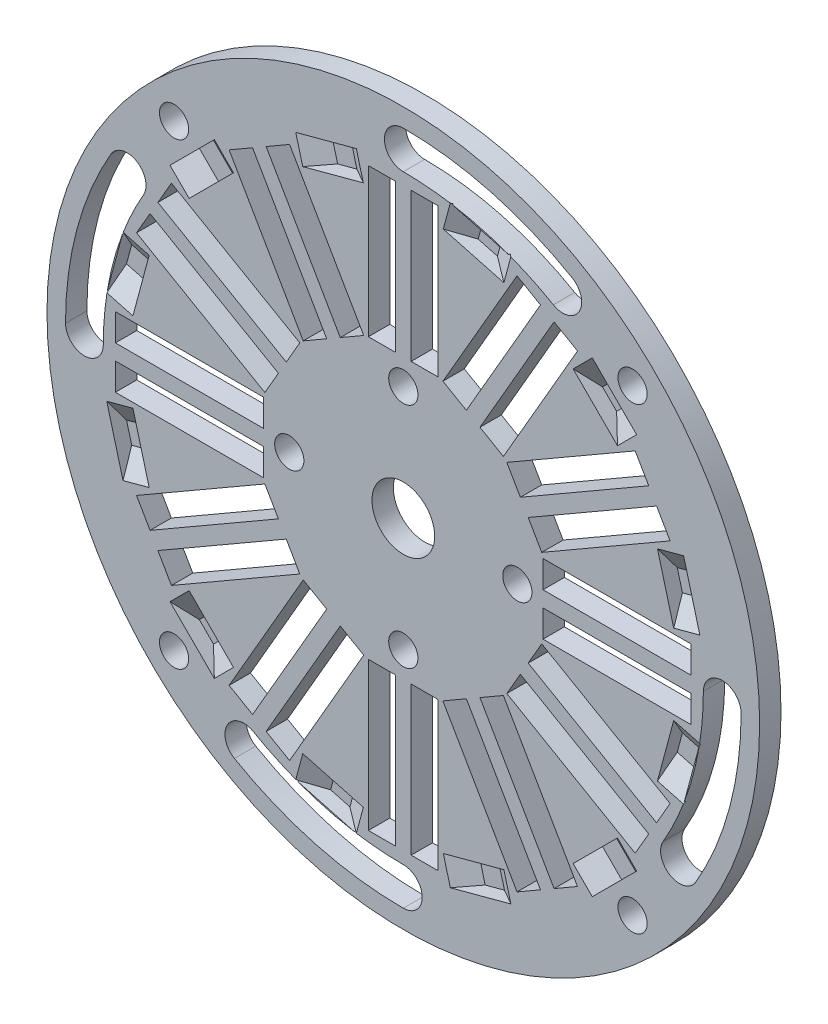
SolidWorks part; units mm, degrees
material "AISI 304"
ref_plane "Alzado" through (0, 0, 0) normal (1, 0, 0) x (0, 1, 0)
ref_plane "Planta" through (0, 0, 0) normal (0, 0, 1) x (0, 1, 0)
ref_plane "Vista lateral" through (0, 0, 0) normal (0, 1, 0) x (-1, 0, 0)
sketch "Croquis1" plane through (0, 0, 0) normal (0, 0, 1) x (0, 1, 0)
  circle A0 centre (0, 0) radius 50
  dimension "D1" = 100
extrude "Saliente-Extruir1" add sketch "Croquis1" along normal blind 3
sketch "Croquis2" plane through (0, 0, 3) normal (0, 0, 1) x (1, 0, 0)
  line L102 (15.9565, 37.4374) -> (5.5565, 19.4241)
  line L103 (-4.9, 40.4) -> (4.9, 40.4)
  line L104 (-4.9, 40.4) -> (-4.9, 19.6)
  line L105 (-4.9, 19.6) -> (4.9, 19.6)
  line L106 (4.9, 40.4) -> (4.9, 19.6)
  line L107 (-4.9, 40.4) -> (4.9, 19.6) construction
  line L108 (-4.9, 19.6) -> (4.9, 40.4) construction
  line L109 (15.9565, 37.4374) -> (24.4435, 32.5374)
  line L110 (24.4435, 32.5374) -> (14.0435, 14.5241)
  line L111 (5.5565, 19.4241) -> (14.0435, 14.5241)
  line L112 (32.5374, 24.4435) -> (14.5241, 14.0435)
  line L113 (32.5374, 24.4435) -> (37.4374, 15.9565)
  line L114 (37.4374, 15.9565) -> (19.4241, 5.5565)
  line L115 (14.5241, 14.0435) -> (19.4241, 5.5565)
  line L116 (40.4, 4.9) -> (19.6, 4.9)
  line L117 (40.4, 4.9) -> (40.4, -4.9)
  line L118 (40.4, -4.9) -> (19.6, -4.9)
  line L119 (19.6, 4.9) -> (19.6, -4.9)
  line L120 (37.4374, -15.9565) -> (19.4241, -5.5565)
  line L121 (37.4374, -15.9565) -> (32.5374, -24.4435)
  line L122 (32.5374, -24.4435) -> (14.5241, -14.0435)
  line L123 (19.4241, -5.5565) -> (14.5241, -14.0435)
  line L124 (24.4435, -32.5374) -> (14.0435, -14.5241)
  line L125 (24.4435, -32.5374) -> (15.9565, -37.4374)
  line L126 (15.9565, -37.4374) -> (5.5565, -19.4241)
  line L127 (14.0435, -14.5241) -> (5.5565, -19.4241)
  line L128 (4.9, -40.4) -> (4.9, -19.6)
  line L129 (4.9, -40.4) -> (-4.9, -40.4)
  line L130 (-4.9, -40.4) -> (-4.9, -19.6)
  line L131 (4.9, -19.6) -> (-4.9, -19.6)
  line L132 (-15.9565, -37.4374) -> (-5.5565, -19.4241)
  line L133 (-15.9565, -37.4374) -> (-24.4435, -32.5374)
  line L135 (-24.4435, -32.5374) -> (-14.0435, -14.5241)
  line L136 (-5.5565, -19.4241) -> (-14.0435, -14.5241)
  line L181 (-32.5374, -24.4435) -> (-14.5241, -14.0435)
  line L182 (-32.5374, -24.4435) -> (-37.4374, -15.9565)
  line L185 (-37.4374, -15.9565) -> (-19.4241, -5.5565)
  line L187 (-14.5241, -14.0435) -> (-19.4241, -5.5565)
  line L188 (-40.4, -4.9) -> (-19.6, -4.9)
  line L192 (-40.4, -4.9) -> (-40.4, 4.9)
  line L206 (-40.4, 4.9) -> (-19.6, 4.9)
  line L212 (-19.6, -4.9) -> (-19.6, 4.9)
  line L213 (-37.4374, 15.9565) -> (-19.4241, 5.5565)
  line L214 (-37.4374, 15.9565) -> (-32.5374, 24.4435)
  line L215 (-32.5374, 24.4435) -> (-14.5241, 14.0435)
  line L216 (-19.4241, 5.5565) -> (-14.5241, 14.0435)
  line L217 (-24.4435, 32.5374) -> (-14.0435, 14.5241)
  line L218 (-24.4435, 32.5374) -> (-15.9565, 37.4374)
  line L219 (-15.9565, 37.4374) -> (-5.5565, 19.4241)
  line L220 (-14.0435, 14.5241) -> (-5.5565, 19.4241)
  point P0 (0, 30)
  point P51 (0, 0)
  dimension "D1" = 9.8
  dimension "D2" = 20.8
  dimension "D3" = 0
  dimension "D4" = 30
  dimension "D5" = 12
extrude "Cortar-Extruir1" cut sketch "Croquis2" against normal through all
sketch "Croquis3" plane through (0, 0, 3) normal (0, 0, 1) x (1, 0, 0)
  line L5 (19.2474, 35.5374) -> (8.8474, 17.5241)
  line L6 (-1.1, 40.4) -> (1.1, 40.4)
  line L51 (19.2474, 35.5374) -> (21.1526, 34.4374)
  line L52 (21.1526, 34.4374) -> (10.7526, 16.4241)
  line L53 (8.8474, 17.5241) -> (10.7526, 16.4241)
  line L54 (34.4374, 21.1526) -> (16.4241, 10.7526)
  line L55 (34.4374, 21.1526) -> (35.5374, 19.2474)
  line L56 (35.5374, 19.2474) -> (17.5241, 8.8474)
  line L61 (-1.1, 40.4) -> (-1.1, 19.6)
  line L63 (-1.1, 19.6) -> (1.1, 19.6)
  line L66 (1.1, 40.4) -> (1.1, 19.6)
  line L67 (-1.1, 40.4) -> (1.1, 19.6) construction
  line L70 (-1.1, 19.6) -> (1.1, 40.4) construction
  line L73 (16.4241, 10.7526) -> (17.5241, 8.8474)
  line L77 (40.4, 1.1) -> (19.6, 1.1)
  line L78 (40.4, 1.1) -> (40.4, -1.1)
  line L82 (40.4, -1.1) -> (19.6, -1.1)
  line L84 (19.6, 1.1) -> (19.6, -1.1)
  line L85 (35.5374, -19.2474) -> (17.5241, -8.8474)
  line L93 (35.5374, -19.2474) -> (34.4374, -21.1526)
  line L95 (34.4374, -21.1526) -> (16.4241, -10.7526)
  line L96 (17.5241, -8.8474) -> (16.4241, -10.7526)
  line L98 (21.1526, -34.4374) -> (10.7526, -16.4241)
  line L105 (21.1526, -34.4374) -> (19.2474, -35.5374)
  line L107 (19.2474, -35.5374) -> (8.8474, -17.5241)
  line L110 (10.7526, -16.4241) -> (8.8474, -17.5241)
  line L111 (1.1, -40.4) -> (1.1, -19.6)
  line L113 (1.1, -40.4) -> (-1.1, -40.4)
  line L114 (-1.1, -40.4) -> (-1.1, -19.6)
  line L115 (1.1, -19.6) -> (-1.1, -19.6)
  line L116 (-19.2474, -35.5374) -> (-8.8474, -17.5241)
  line L117 (-19.2474, -35.5374) -> (-21.1526, -34.4374)
  line L118 (-21.1526, -34.4374) -> (-10.7526, -16.4241)
  line L119 (-8.8474, -17.5241) -> (-10.7526, -16.4241)
  line L120 (-34.4374, -21.1526) -> (-16.4241, -10.7526)
  line L121 (-34.4374, -21.1526) -> (-35.5374, -19.2474)
  line L122 (-35.5374, -19.2474) -> (-17.5241, -8.8474)
  line L123 (-16.4241, -10.7526) -> (-17.5241, -8.8474)
  line L124 (-40.4, -1.1) -> (-19.6, -1.1)
  line L125 (-40.4, -1.1) -> (-40.4, 1.1)
  line L126 (-40.4, 1.1) -> (-19.6, 1.1)
  line L127 (-19.6, -1.1) -> (-19.6, 1.1)
  line L128 (-35.5374, 19.2474) -> (-17.5241, 8.8474)
  line L129 (-35.5374, 19.2474) -> (-34.4374, 21.1526)
  line L130 (-34.4374, 21.1526) -> (-16.4241, 10.7526)
  line L131 (-17.5241, 8.8474) -> (-16.4241, 10.7526)
  line L132 (-21.1526, 34.4374) -> (-10.7526, 16.4241)
  line L133 (-21.1526, 34.4374) -> (-19.2474, 35.5374)
  line L134 (-19.2474, 35.5374) -> (-8.8474, 17.5241)
  line L135 (-10.7526, 16.4241) -> (-8.8474, 17.5241)
  point P0 (0, 30)
  point P52 (0, 0)
  dimension "D1" = 2.2
  dimension "D2" = 30
  dimension "D3" = 12
  dimension "D4" = 20.8
extrude "Saliente-Extruir2" add sketch "Croquis3" against normal blind 3
sketch "Croquis5" plane through (0, 0, 3) normal (0, 0, 1) x (1, 0, 0)
  circle A0 centre (0, 0) radius 4.4
  circle A1 centre (0, 44.75) radius 2.65
  circle A2 centre (44.75, 0) radius 2.65
  circle A3 centre (0, -44.75) radius 2.65
  circle A4 centre (-44.75, 0) radius 2.65
  point P19 (0, 0)
  dimension "D2" = 8.8
  dimension "D3" = 5.3
  dimension "D5" = 5.3
  dimension "D1" = 44.75
  dimension "D4" = 4
extrude "Cortar-Extruir3" cut sketch "Croquis5" against normal blind 10
sketch "Croquis6" plane through (0, 0, 3) normal (0, 0, 1) x (1, 0, 0)
  line L0 (0, 0) -> (28.2843, 28.2843) construction
  line L6 (26.5165, 32.739) -> (32.739, 26.5165)
  line L7 (26.5165, 32.739) -> (23.8295, 30.052)
  line L52 (23.8295, 30.052) -> (30.052, 23.8295)
  line L53 (32.739, 26.5165) -> (30.052, 23.8295)
  line L54 (26.5165, 32.739) -> (30.052, 23.8295) construction
  line L55 (23.8295, 30.052) -> (32.739, 26.5165) construction
  line L56 (39.3335, 15.0946) -> (35.663, 14.1111)
  line L57 (39.3335, 15.0946) -> (41.6111, 6.5944)
  line L58 (41.6111, 6.5944) -> (37.9406, 5.6109)
  line L59 (35.663, 14.1111) -> (37.9406, 5.6109)
  line L60 (39.3335, 15.0946) -> (37.9406, 5.6109) construction
  line L61 (35.663, 14.1111) -> (41.6111, 6.5944) construction
  line L62 (41.6111, -6.5944) -> (37.9406, -5.6109)
  line L63 (41.6111, -6.5944) -> (39.3335, -15.0946)
  line L64 (39.3335, -15.0946) -> (35.663, -14.1111)
  line L65 (37.9406, -5.6109) -> (35.663, -14.1111)
  line L66 (41.6111, -6.5944) -> (35.663, -14.1111) construction
  line L67 (37.9406, -5.6109) -> (39.3335, -15.0946) construction
  line L68 (32.739, -26.5165) -> (30.052, -23.8295)
  line L69 (32.739, -26.5165) -> (26.5165, -32.739)
  line L70 (26.5165, -32.739) -> (23.8295, -30.052)
  line L71 (30.052, -23.8295) -> (23.8295, -30.052)
  line L72 (32.739, -26.5165) -> (23.8295, -30.052) construction
  line L73 (30.052, -23.8295) -> (26.5165, -32.739) construction
  line L74 (15.0946, -39.3335) -> (14.1111, -35.663)
  line L75 (15.0946, -39.3335) -> (6.5944, -41.6111)
  line L76 (6.5944, -41.6111) -> (5.6109, -37.9406)
  line L77 (14.1111, -35.663) -> (5.6109, -37.9406)
  line L78 (15.0946, -39.3335) -> (5.6109, -37.9406) construction
  line L79 (14.1111, -35.663) -> (6.5944, -41.6111) construction
  line L80 (-6.5944, -41.6111) -> (-5.6109, -37.9406)
  line L81 (-6.5944, -41.6111) -> (-15.0946, -39.3335)
  line L82 (-15.0946, -39.3335) -> (-14.1111, -35.663)
  line L83 (-5.6109, -37.9406) -> (-14.1111, -35.663)
  line L84 (-6.5944, -41.6111) -> (-14.1111, -35.663) construction
  line L85 (-5.6109, -37.9406) -> (-15.0946, -39.3335) construction
  line L86 (-26.5165, -32.739) -> (-23.8295, -30.052)
  line L87 (-26.5165, -32.739) -> (-32.739, -26.5165)
  line L88 (-32.739, -26.5165) -> (-30.052, -23.8295)
  line L89 (-23.8295, -30.052) -> (-30.052, -23.8295)
  line L90 (-26.5165, -32.739) -> (-30.052, -23.8295) construction
  line L91 (-23.8295, -30.052) -> (-32.739, -26.5165) construction
  line L92 (-39.3335, -15.0946) -> (-35.663, -14.1111)
  line L93 (-39.3335, -15.0946) -> (-41.6111, -6.5944)
  line L94 (-41.6111, -6.5944) -> (-37.9406, -5.6109)
  line L95 (-35.663, -14.1111) -> (-37.9406, -5.6109)
  line L96 (-39.3335, -15.0946) -> (-37.9406, -5.6109) construction
  line L97 (-35.663, -14.1111) -> (-41.6111, -6.5944) construction
  line L98 (-41.6111, 6.5944) -> (-37.9406, 5.6109)
  line L99 (-41.6111, 6.5944) -> (-39.3335, 15.0946)
  line L100 (-39.3335, 15.0946) -> (-35.663, 14.1111)
  line L101 (-37.9406, 5.6109) -> (-35.663, 14.1111)
  line L102 (-41.6111, 6.5944) -> (-35.663, 14.1111) construction
  line L103 (-37.9406, 5.6109) -> (-39.3335, 15.0946) construction
  line L104 (-32.739, 26.5165) -> (-30.052, 23.8295)
  line L105 (-32.739, 26.5165) -> (-26.5165, 32.739)
  line L106 (-26.5165, 32.739) -> (-23.8295, 30.052)
  line L107 (-30.052, 23.8295) -> (-23.8295, 30.052)
  line L108 (-32.739, 26.5165) -> (-23.8295, 30.052) construction
  line L109 (-30.052, 23.8295) -> (-26.5165, 32.739) construction
  line L110 (-15.0946, 39.3335) -> (-14.1111, 35.663)
  line L111 (-15.0946, 39.3335) -> (-6.5944, 41.6111)
  line L112 (-6.5944, 41.6111) -> (-5.6109, 37.9406)
  line L113 (-14.1111, 35.663) -> (-5.6109, 37.9406)
  line L114 (-15.0946, 39.3335) -> (-5.6109, 37.9406) construction
  line L115 (-14.1111, 35.663) -> (-6.5944, 41.6111) construction
  line L116 (6.5944, 41.6111) -> (5.6109, 37.9406)
  line L117 (6.5944, 41.6111) -> (15.0946, 39.3335)
  line L118 (15.0946, 39.3335) -> (14.1111, 35.663)
  line L119 (5.6109, 37.9406) -> (14.1111, 35.663)
  line L120 (6.5944, 41.6111) -> (14.1111, 35.663) construction
  line L121 (5.6109, 37.9406) -> (15.0946, 39.3335) construction
  point P0 (28.2843, 28.2843)
  point P57 (0, 0)
  dimension "D1" = 8.8
  dimension "D2" = 3.8
extrude "Cortar-Extruir4" cut sketch "Croquis6" against normal blind 2
chamfer "Chaflán3" distance 2 distance2 3 12 edges at (6.1027, 39.7758, 1) (25.173, 31.3955, 1) (37.4982, 14.6028, 1) (39.7758, -6.1027, 1) (31.3955, -25.173, 1) (14.6028, -37.4982, 1) (-6.1027, -39.7758, 1) (-25.173, -31.3955, 1) (-37.4982, -14.6028, 1) (-14.6028, 37.4982, 1) (-31.3955, 25.173, 1) (-39.7758, 6.1027, 1) first distance on face at (6.1027, 39.7758, 2) first distance on face at (25.173, 31.3955, 2) first distance on face at (37.4982, 14.6028, 2) first distance on face at (39.7758, -6.1027, 2) first distance on face at (31.3955, -25.173, 2) first distance on face at (14.6028, -37.4982, 2) first distance on face at (-6.1027, -39.7758, 2) first distance on face at (-25.173, -31.3955, 2) first distance on face at (-37.4982, -14.6028, 2) first distance on face at (-14.6028, 37.4982, 2) first distance on face at (-31.3955, 25.173, 2) first distance on face at (-39.7758, 6.1027, 2)
chamfer "Chaflán4" distance 2 distance2 3 12 edges at (6.1027, -39.7758, 1) (25.173, -31.3955, 1) (37.4982, -14.6028, 1) (39.7758, 6.1027, 1) (31.3955, 25.173, 1) (14.6028, 37.4982, 1) (-6.1027, 39.7758, 1) (-25.173, 31.3955, 1) (-37.4982, 14.6028, 1) (-14.6028, -37.4982, 1) (-39.7758, -6.1027, 1) (-31.3955, -25.173, 1) first distance on face at (6.1027, -39.7758, 2) first distance on face at (25.173, -31.3955, 2) first distance on face at (37.4982, -14.6028, 2) first distance on face at (39.7758, 6.1027, 2) first distance on face at (31.3955, 25.173, 2) first distance on face at (14.6028, 37.4982, 2) first distance on face at (-6.1027, 39.7758, 2) first distance on face at (-25.173, 31.3955, 2) first distance on face at (-37.4982, 14.6028, 2) first distance on face at (-14.6028, -37.4982, 2) first distance on face at (-39.7758, -6.1027, 2) first distance on face at (-31.3955, -25.173, 2)
sketch "Croquis7" plane through (0, 0, 3) normal (0, 0, 1) x (1, 0, 0)
  arc A0 (0, 47.4) -> (0, 42.1) centre (0, 44.75) ccw
  arc A1 (21.05, 36.4597) -> (23.7, 41.0496) centre (22.375, 38.7546) ccw
  arc A2 (23.7, 41.0496) -> (0, 47.4) centre (0, 0) ccw
  arc A3 (21.05, 36.4597) -> (0, 42.1) centre (0, 0) ccw
  arc A4 (47.4, 0) -> (42.1, 0) centre (44.75, 0) ccw
  arc A5 (36.4597, -21.05) -> (42.1, 0) centre (0, 0) ccw
  arc A6 (36.4597, -21.05) -> (41.0496, -23.7) centre (38.7546, -22.375) ccw
  arc A7 (41.0496, -23.7) -> (47.4, 0) centre (0, 0) ccw
  arc A8 (0, -47.4) -> (0, -42.1) centre (0, -44.75) ccw
  arc A9 (-21.05, -36.4597) -> (0, -42.1) centre (0, 0) ccw
  arc A10 (-21.05, -36.4597) -> (-23.7, -41.0496) centre (-22.375, -38.7546) ccw
  arc A11 (-23.7, -41.0496) -> (0, -47.4) centre (0, 0) ccw
  arc A12 (-47.4, 0) -> (-42.1, 0) centre (-44.75, 0) ccw
  arc A13 (-36.4597, 21.05) -> (-42.1, 0) centre (0, 0) ccw
  arc A14 (-36.4597, 21.05) -> (-41.0496, 23.7) centre (-38.7546, 22.375) ccw
  arc A15 (-41.0496, 23.7) -> (-47.4, 0) centre (0, 0) ccw
  point P8 (0, 0)
  point P31 (0, 0)
  dimension "D2" = 5.3
  dimension "D4" = 2.65
  dimension "D5" = 2.65
  dimension "D1" = 2
  dimension "D3" = 4
extrude "Cortar-Extruir5" cut sketch "Croquis7" against normal blind 10
sketch "Croquis8" plane through (0, 0, 3) normal (0, 0, 1) x (1, 0, 0)
  circle A0 centre (0, 16) radius 2.05
  circle A1 centre (16, 0) radius 2.05
  circle A2 centre (0, -16) radius 2.05
  circle A3 centre (-16, 0) radius 2.05
  point P12 (0, 0)
  dimension "D1" = 4.1
  dimension "D2" = 16
  dimension "D3" = 4
extrude "Cortar-Extruir6" cut sketch "Croquis8" against normal through all
cosmetic thread "Rosca cosmética1" parameters "D2"=5
cosmetic thread "Rosca cosmética2" parameters "D2"=5
cosmetic thread "Rosca cosmética3" parameters "D2"=5
cosmetic thread "Rosca cosmética4" parameters "D2"=5
sketch "Croquis9" plane through (0, 0, 3) normal (0, 0, 1) x (1, 0, 0)
  circle A0 centre (-32.17, 32.17) radius 2.05
  circle A1 centre (32.17, 32.17) radius 2.05
  circle A2 centre (32.17, -32.17) radius 2.05
  circle A3 centre (-32.17, -32.17) radius 2.05
  point P12 (0, 0)
  dimension "D1" = 4.1
  dimension "D2" = 32.17
  dimension "D3" = 32.17
  dimension "D4" = 4
extrude "Cortar-Extruir7" cut sketch "Croquis9" against normal through all
cosmetic thread "Rosca cosmética5" parameters "D2"=5
cosmetic thread "Rosca cosmética6" parameters "D2"=5
cosmetic thread "Rosca cosmética7" parameters "D2"=5
cosmetic thread "Rosca cosmética8" parameters "D2"=5
